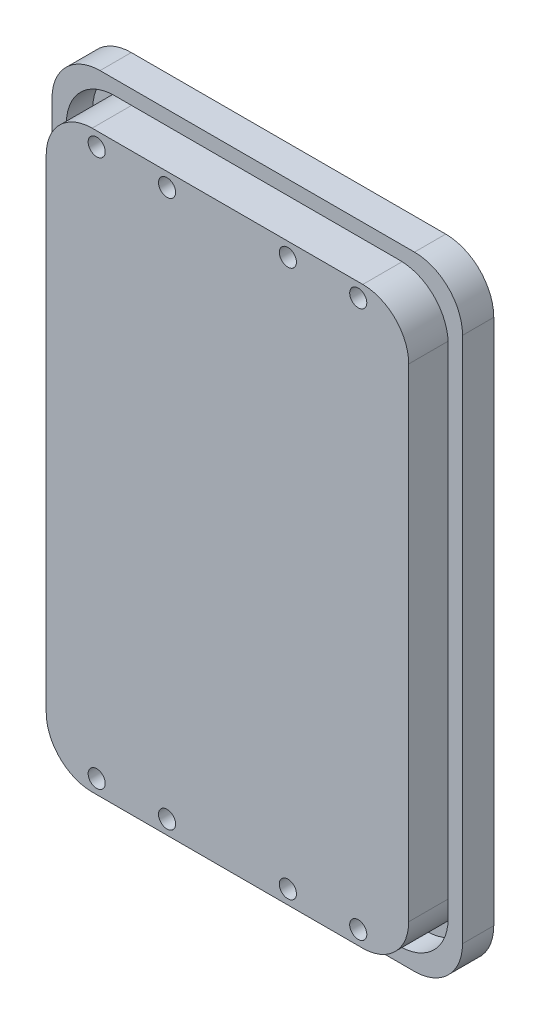
SolidWorks part; units mm, degrees
ref_plane "前视基准面" through (0, 0, 0) normal (0, 0, 1) x (1, 0, 0)
ref_plane "上视基准面" through (0, 0, 0) normal (0, 1, 0) x (1, 0, 0)
ref_plane "右视基准面" through (0, 0, 0) normal (1, 0, 0) x (0, 0, -1)
sketch "basis" plane through (0, 0, 0) normal (0, 0, 1) x (1, 0, 0)
  line L1 (-28.1566, 59.81) -> (28.1566, 59.81)
  line L2 (-37.71, 50.2566) -> (-37.71, -50.2566)
  line L3 (-28.1566, -59.81) -> (28.1566, -59.81)
  line L4 (37.71, 50.2566) -> (37.71, -50.2566)
  line L5 (-37.71, 59.81) -> (37.71, -59.81) construction
  line L6 (-37.71, -59.81) -> (37.71, 59.81) construction
  line L7 (-29.71, 61.81) -> (29.71, 61.81)
  line L8 (-39.71, 51.81) -> (-39.71, -51.81)
  line L9 (-29.71, -61.81) -> (29.71, -61.81)
  line L10 (39.71, 51.81) -> (39.71, -51.81)
  line L11 (-39.71, 61.81) -> (39.71, -61.81) construction
  line L12 (-39.71, -61.81) -> (39.71, 61.81) construction
  line L13 (-32.71, 64.81) -> (32.71, 64.81)
  line L14 (-42.71, 54.81) -> (-42.71, -54.81)
  line L15 (-32.71, -64.81) -> (32.71, -64.81)
  line L16 (42.71, 54.81) -> (42.71, -54.81)
  line L17 (-42.71, 64.81) -> (42.71, -64.81) construction
  line L18 (-42.71, -64.81) -> (42.71, 64.81) construction
  arc A0 (28.1566, -59.81) -> (37.71, -50.2566) centre (28.1566, -50.2566) ccw
  arc A1 (-37.71, -50.2566) -> (-28.1566, -59.81) centre (-28.1566, -50.2566) ccw
  arc A2 (28.1566, 59.81) -> (37.71, 50.2566) centre (28.1566, 50.2566) cw
  arc A3 (-28.1566, 59.81) -> (-37.71, 50.2566) centre (-28.1566, 50.2566) ccw
  arc A4 (32.71, -64.81) -> (42.71, -54.81) centre (32.71, -54.81) ccw
  arc A5 (29.71, -61.81) -> (39.71, -51.81) centre (29.71, -51.81) ccw
  arc A6 (-42.71, -54.81) -> (-32.71, -64.81) centre (-32.71, -54.81) ccw
  arc A7 (-39.71, -51.81) -> (-29.71, -61.81) centre (-29.71, -51.81) ccw
  arc A8 (-29.71, 61.81) -> (-39.71, 51.81) centre (-29.71, 51.81) ccw
  arc A9 (-32.71, 64.81) -> (-42.71, 54.81) centre (-32.71, 54.81) ccw
  arc A10 (32.71, 64.81) -> (42.71, 54.81) centre (32.71, 54.81) cw
  arc A11 (29.71, 61.81) -> (39.71, 51.81) centre (29.71, 51.81) cw
  point P0 (0, 0)
  point P6 (0, 0)
  point P11 (0, 0)
  dimension "D7" = 9.5534
  dimension "D8" = 10
  dimension "D1" = 129.62
  dimension "D2" = 85.42
  dimension "D3" = 79.42
  dimension "D4" = 123.62
  dimension "D5" = 119.62
  dimension "D6" = 75.42
extrude "凸台-拉伸2" add sketch "basis" along normal blind 6.5 contours A10 L13 A9 L14 A6 L15 A4 L16 L7 A11 L10 A5 L9 A7 L8 A8 region at (0, 63.2576, 0)
extrude "凸台-拉伸3" add sketch "basis<4>" along normal blind 12.7 separate body contours L1 A3 L2 A1 L3 A0 L4 A2 region at (0, 0, 0)
sketch "basis<4>" plane through (0, 0, 0) normal (0, 0, 1) x (1, 0, 0) same geometry as "basis"
extrude "凸台-拉伸4" add sketch "basis<5>" along normal blind 1 contours A11 L7 A8 L8 A7 L9 A5 L10 A3 L1 A2 L4 A0 L3 A1 L2 region at (0, 60.3407, 0)
sketch "basis<5>" plane through (0, 0, 0) normal (0, 0, 1) x (1, 0, 0) same geometry as "basis"
sketch "草图5" plane through (0, 0, 0) normal (0, 0, -1) x (-1, 0, 0)
  circle A0 centre (27.21, 56.91) radius 1.78
  circle A1 centre (12.57, 56.91) radius 1.78
  circle A2 centre (-12.57, 56.91) radius 1.78
  circle A3 centre (-27.21, 56.91) radius 1.78
  circle A4 centre (27.21, -56.91) radius 1.78
  circle A5 centre (12.57, -56.91) radius 1.78
  circle A6 centre (-12.57, -56.91) radius 1.78
  circle A7 centre (-27.21, -56.91) radius 1.78
  point P16 (0, 0)
extrude "切除-拉伸1" cut sketch "草图5" against normal through all
